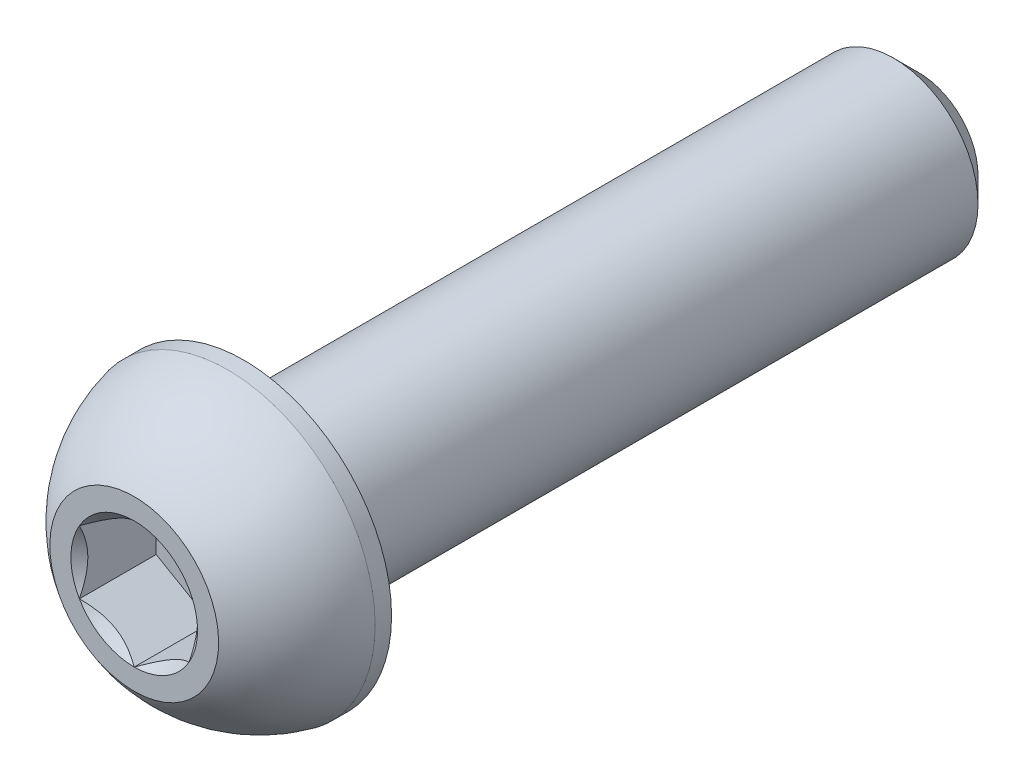
SolidWorks part; units mm, degrees
ref_plane "Front" through (0, 0, 0) normal (0, 0, 1) x (1, 0, 0)
ref_plane "Top" through (0, 0, 0) normal (0, 1, 0) x (1, 0, 0)
ref_plane "Right" through (0, 0, 0) normal (1, 0, 0) x (0, 0, -1)
sketch "Sketch1" plane through (0, 0, 0) normal (1, 0, 0) x (0, 0, -1)
  line L2 (1.3, 1) -> (9.3, 1)
  line L3 (9.3, 1) -> (9.3, 0)
  line L4 (9.3, 0) -> (1.3, 0)
  line L6 (1.105, 1.75) -> (1.3, 1.75) construction
  line L7 (9.3, 1) -> (9.3, -1) construction
  line L8 (0, 0) -> (1.3, 0) construction
  line L9 (1.3, 1.75) -> (1.3, -1.75) construction
  line L11 (1.3, 1) -> (1.3, 0)
  line L13 (0, 0.65) -> (0, -0.65) construction
  line L14 (0, 0.65) -> (0, 1) construction
  line L15 (9.275, 1.0433) -> (9.475, 0.6969) construction
  line L16 (9.475, 0.6969) -> (9.675, 1.0433) construction
  line L17 (9.675, 1.0433) -> (9.275, 1.0433) construction
  line L18 (9.3, 1) -> (9.65, 1) construction
  line L19 (9.475, 1.0433) -> (9.475, 1) construction
  line L20 (9.475, 1) -> (9.475, 0.7402) construction
  line L21 (9.475, 0.7402) -> (9.475, 0.6969) construction
  line L22 (9.45, 0.7402) -> (9.5, 0.7402)
  line L23 (9.2875, 1.0217) -> (9.6625, 1.0217)
  line L24 (9.5, 0.7402) -> (9.6625, 1.0217)
  line L25 (9.45, 0.7402) -> (9.2875, 1.0217)
  line L26 (9, 1) -> (9.3, 0.7)
  arc A3 (0, 1) -> (1.105, 1.75) centre (1.4858, 0) cw construction
  point P29 (9.475, 1.0217)
  point P30 (8.3, -1)
  dimension "D1" = 0.195
  dimension "Pitch" = 0.4
  dimension "D3" = 0.05
  dimension "D2" = 0.3
  dimension "D4" = 45
  dimension "D5" = 1
sketch "Sketch10" plane through (0, 0, 0) normal (1, 0, 0) x (0, 0, -1)
  line L0 (9, 1) -> (9.3, 0.7) construction
  line L1 (9, 1) -> (9.3, 0.7)
  line L4 (9.3, 1) -> (1.3, 1)
  line L5 (9.3, 0) -> (9.3, 1)
  line L6 (1.3, 0) -> (9.3, 0)
  line L7 (1.3, 1) -> (1.3, 0)
  line L8 (9, 1) -> (1.3, 1)
  line L9 (9.3, 0) -> (9.3, 0.7)
  line L10 (1.3, 0) -> (9.3, 0)
  line L11 (1.3, 1) -> (1.3, 0)
  dimension "D1" = 0
revolve "Revolve3" add sketch "Sketch10" angle 360 about L8
sketch "Sketch7" plane through (0, 0, 0) normal (1, 0, 0) x (0, 0, -1)
  line L6 (1.105, 1.75) -> (1.3, 1.75) construction
  line L8 (0, 0) -> (1.3, 0) construction
  line L11 (1.3, 1.75) -> (1.3, -1.75) construction
  line L12 (1.105, 1.75) -> (1.3, 1.75)
  line L13 (0, 0) -> (1.3, 0)
  line L14 (0, 0.65) -> (0, -0.65) construction
  line L15 (1.3, 1.75) -> (1.3, 0)
  line L16 (0, 1) -> (0, 0)
  arc A2 (1.105, 1.75) -> (0, 1) centre (1.4858, 0) ccw construction
  arc A3 (1.105, 1.75) -> (0, 1) centre (1.4858, 0) ccw
revolve "Revolve2" add sketch "Sketch7" angle 360 mid plane about L13
sketch "Sketch5" plane through (0, 0, 0) normal (0, 0, 1) x (1, 0, 0)
  line L1 (0.65, -0.3753) -> (0.65, 0.3753)
  line L2 (0.65, 0.3753) -> (0, 0.7506)
  line L3 (0, 0.7506) -> (-0.65, 0.3753)
  line L4 (-0.65, 0.3753) -> (-0.65, -0.3753)
  line L5 (-0.65, -0.3753) -> (0, -0.7506)
  line L6 (0, -0.7506) -> (0.65, -0.3753)
  circle A0 centre (0, 0) radius 0.65 construction
extrude "Cut-Extrude2" cut sketch "Sketch5" against normal blind 0.91
sketch "Sketch6" plane through (0, 0, 0) normal (0, 0, 1) x (1, 0, 0)
  circle A0 centre (0, 0) radius 0.7506
extrude "Cut-Extrude3" cut sketch "Sketch6" against normal blind 0.91 draft 45
sketch "Sketch9" [suppressed] plane through (0, 0, -1.3) normal (0, 0, -1) x (-1, 0, 0)
  circle A0 centre (0, 0) radius 1 construction
  circle A4 centre (0, 0) radius 1
split "Split1" [suppressed] bodies to split 113
sketch "Sketch11" [suppressed] plane through (0, 0, -9.3) normal (0, 0, -1) x (-1, 0, 0)
  circle A0 centre (0, 0) radius 1 construction
  circle A1 centre (0, 0) radius 1
curve "Helix/Spiral1" [suppressed] pitch 0.4 height 9.3 turns 23.25
sketch "Sketch12" [suppressed] plane through (0, 0, 0) normal (1, 0, 0) x (0, 0, -1)
  line L0 (9.45, 0.7402) -> (9.5, 0.7402) construction
  line L1 (9.5, 0.7402) -> (9.6625, 1.0217) construction
  line L2 (9.2875, 1.0217) -> (9.6625, 1.0217) construction
  line L3 (9.45, 0.7402) -> (9.2875, 1.0217) construction
  line L4 (9.45, 0.7402) -> (9.5, 0.7402)
  line L5 (9.5, 0.7402) -> (9.6625, 1.0217)
  line L6 (9.2875, 1.0217) -> (9.6625, 1.0217)
  line L7 (9.45, 0.7402) -> (9.2875, 1.0217)
sweep "Cut-Sweep2" [suppressed] cut profiles "Sketch12" path "Helix/Spiral1"
extrude "Boss-Extrude1" [suppressed] add sketch "Sketch9" along normal blind 10 draft 45
equation "\"D1@Cut-Extrude2\" = \"Head Ht@Sketch1\" * .7"
equation "\"D1@Sketch1\" = \"Head Ht@Sketch1\" * .15"
equation "\"D1@Cut-Extrude3\" = \"D1@Cut-Extrude2\""
equation "\"D3@Sketch1\" = \"Pitch@Sketch1\" / 8"
equation "\"D2@Sketch1\"=\"Pitch@Sketch1\"*0.75"
equation "\"D3@Helix/Spiral1\" = \"Lg@Sketch1\" + \"Head Ht@Sketch1\""
equation "\"D4@Helix/Spiral1\"=\"pitch@sketch1\""
equation "\"D5@Sketch1\"=\"Pitch@Sketch1\"*2.5"
